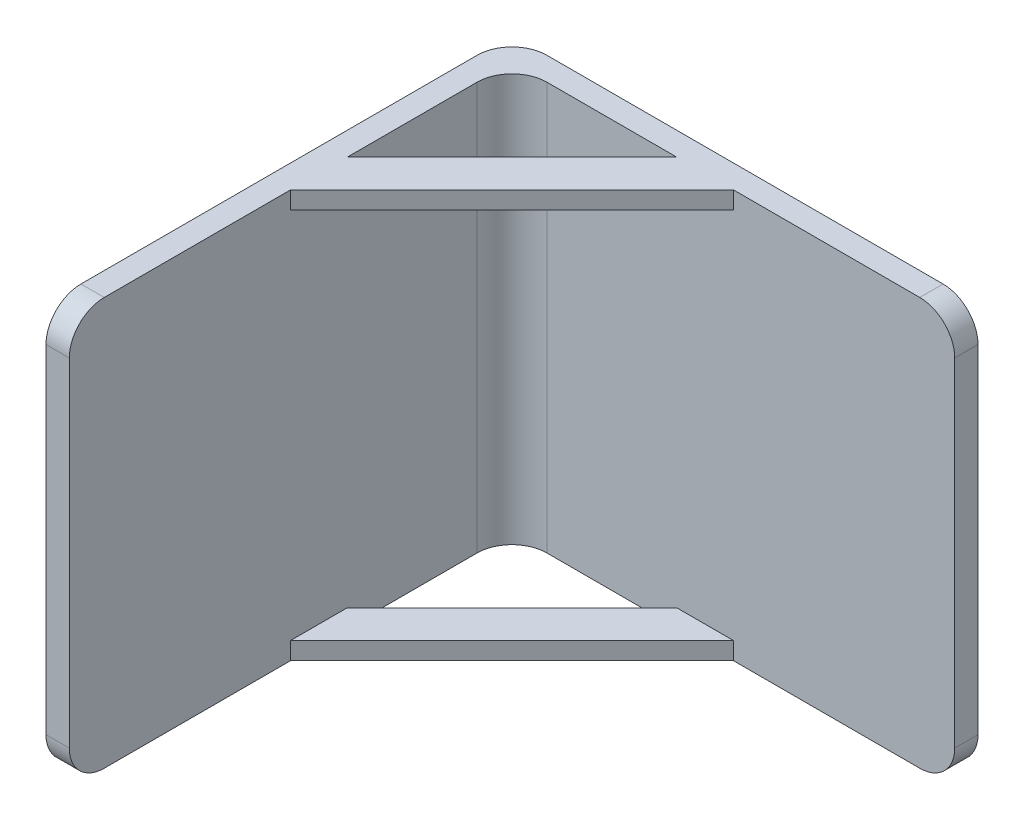
SolidWorks part; units mm, degrees
material "Stainless Steel (ferritic)"
ref_plane "Front Plane" through (0, 0, 0) normal (0, 0, 1) x (1, 0, 0)
ref_plane "Top Plane" through (0, 0, 0) normal (0, 1, 0) x (1, 0, 0)
ref_plane "Right Plane" through (0, 0, 0) normal (1, 0, 0) x (0, 0, -1)
sketch "Sketch1" plane through (0, 0, 0) normal (0, 0, 1) x (1, 0, 0)
  line L1 (-20, -17.5) -> (20, -17.5)
  line L2 (-20, -17.5) -> (-20, 17.5)
  line L3 (-20, 17.5) -> (20, 17.5)
  line L4 (20, -17.5) -> (20, 17.5)
  line L5 (-20, -17.5) -> (20, 17.5) construction
  line L6 (-20, 17.5) -> (20, -17.5) construction
  point P0 (0, 0)
  dimension "D1" = 40
  dimension "D2" = 35
extrude "Boss-Extrude1" add sketch "Sketch1" along normal blind 2
sketch "Sketch2" plane through (0, 0, 2) normal (0, 0, 1) x (1, 0, 0)
  line L0 (-20, 17.5) -> (-20, -17.5)
  line L1 (-20, 17.5) -> (-18, 17.5)
  line L2 (-20, -17.5) -> (-18, -17.5)
  line L3 (-18, 17.5) -> (-18, -17.5)
  dimension "D1" = 2
extrude "Boss-Extrude2" add sketch "Sketch2" along normal blind 38
fillet "Fillet1" radius 3 6 edges at (-20, 0, 0) (-18, 0, 2) (20, 17.5, 1) (20, -17.5, 1) (-19, 17.5, 40) (-19, -17.5, 40)
sketch "Sketch3" plane through (0, -17.5, 0) normal (0, -1, 0) x (1, 0, 0)
  line L0 (1, 2) -> (-18, 21)
  line L1 (-15, 2) -> (17, 2) construction
  line L2 (-18, 37) -> (-18, 5) construction
  line L3 (-18, 16.1421) -> (-3.8579, 2)
  line L4 (-18, 21) -> (-18, 16.1421)
  line L5 (-3.8579, 2) -> (1, 2)
  dimension "D1" = 45
  dimension "D2" = 20
extrude "Boss-Extrude3" add sketch "Sketch3" against normal blind 1.5
extrude "Boss-Extrude4" add sketch "Sketch3<2>" against normal blind 1.5 from offset 33.5 offset against normal yes
sketch "Sketch3<2>" plane through (0, -17.5, 0) normal (0, -1, 0) x (1, 0, 0) same geometry as "Sketch3"
sketch "Sketch4" plane through (-18, 0, 0) normal (1, 0, 0) x (0, 0, -1)
  line L0 (-40, 0) -> (-5, 0) construction
  line L1 (-40, -14.5) -> (-40, 14.5) construction
  line L2 (-5, -17.5) -> (-5, 17.5) construction
  point P6 (-30, 7.5)
  point P7 (-15, 7.5)
  point P8 (-15, -7.5)
  point P9 (-30, -7.5)
  point P10 (0, 0)
  dimension "D1" = 7.5
  dimension "D2" = 10
  dimension "D3" = 7.5
  dimension "D4" = 25
sketch "Sketch5" plane through (0, 0, 2) normal (0, 0, 1) x (1, 0, 0)
  line L0 (20, 0) -> (-15, 0) construction
  line L1 (20, -14.5) -> (20, 14.5) construction
  line L2 (-15, 17.5) -> (-15, -17.5) construction
  point P6 (-5, 7.5)
  point P7 (10, 7.5)
  point P8 (-5, -7.5)
  point P9 (10, -7.5)
  point P10 (0, 0)
  dimension "D1" = 25
  dimension "D2" = 10
  dimension "D3" = 7.5
  dimension "D4" = 7.5
